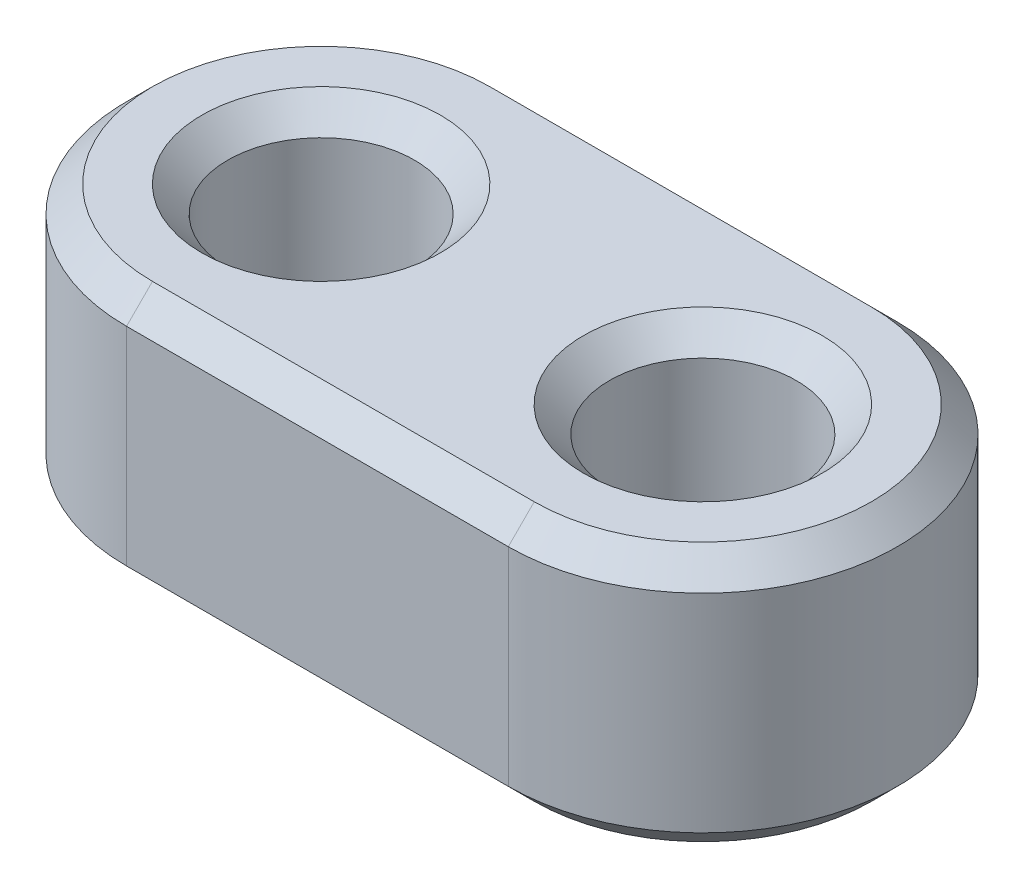
SolidWorks part; units mm, degrees
ref_plane "Front Plane" through (0, 0, 0) normal (0, 0, 1) x (1, 0, 0)
ref_plane "Top Plane" through (0, 0, 0) normal (0, 1, 0) x (1, 0, 0)
ref_plane "Right Plane" through (0, 0, 0) normal (1, 0, 0) x (0, 0, -1)
sketch "Sketch2" plane through (0, 0, 0) normal (0, 1, 0) x (1, 0, 0)
  line L0 (0, 4.7625) -> (14.1051, 4.7625)
  line L1 (14.1051, 4.7625) -> (14.1051, -4.7625)
  line L2 (14.1051, -4.7625) -> (0, -4.7625)
  arc A0 (0, 4.7625) -> (0, -4.7625) centre (0, 0) ccw
  circle A1 centre (0, 0) radius 2.286
  dimension "D1" = 4.572
  dimension "D2" = 4.7625
extrude "Boss-Extrude1" add sketch "Sketch2" along normal blind 6.35
sketch "Sketch3" plane through (14.1051, 0, 0) normal (1, 0, 0) x (0, 0, -1)
  circle A0 centre (0, 3.0961) radius 2.032
  dimension "D1" = 4.064
extrude "Cut-Extrude1" [suppressed] cut sketch "Sketch3" against normal blind 9.525
sketch "Sketch4" plane through (0, 6.35, 0) normal (0, 1, 0) x (1, 0, 0)
  line L0 (14.1051, -4.7625) -> (14.1051, 4.7625) construction
  line L1 (14.1051, 4.7625) -> (0, 4.7625) construction
  line L2 (0, -4.7625) -> (14.1051, -4.7625) construction
  line L3 (9.3426, 4.7625) -> (14.1051, 4.7625)
  line L4 (14.1051, 4.7625) -> (14.1051, -4.7625)
  line L5 (14.1051, -4.7625) -> (9.3426, -4.7625)
  circle A0 centre (9.3426, 0) radius 2.286
  circle A1 centre (0, 0) radius 2.286 construction
  arc A2 (9.3426, 4.7625) -> (9.3426, -4.7625) centre (9.3426, 0) cw
  point P8 (14.1051, 0)
  line M3 (0, -4.7625) -> (14.1051, -4.7625)
  line M4 (14.1051, -4.7625) -> (14.1051, 4.7625)
  line M5 (14.1051, 4.7625) -> (0, 4.7625)
  dimension "D1" = 4.7625
extrude "Cut-Extrude2" cut sketch "Sketch4" against normal through all contours A2 L4 M5 | A2 M4 M3 | A0 region at (13.0413, 6.35, 3.6987) region at (13.0413, 6.35, -3.6987) region at (9.3426, 6.35, 0)
chamfer "Chamfer1" distance 0.635 angle 45 12 edges at (0, 0, 2.286) (0, 6.35, 2.286) (9.3426, 6.35, 2.286) (9.3426, 0, 2.286) (4.6713, 0, -4.7625) (-4.7625, 0, 0) (14.1051, 0, 0) (4.6713, 0, 4.7625) (4.6713, 6.35, -4.7625) (-4.7625, 6.35, 0) (14.1051, 6.35, 0) (4.6713, 6.35, 4.7625)
